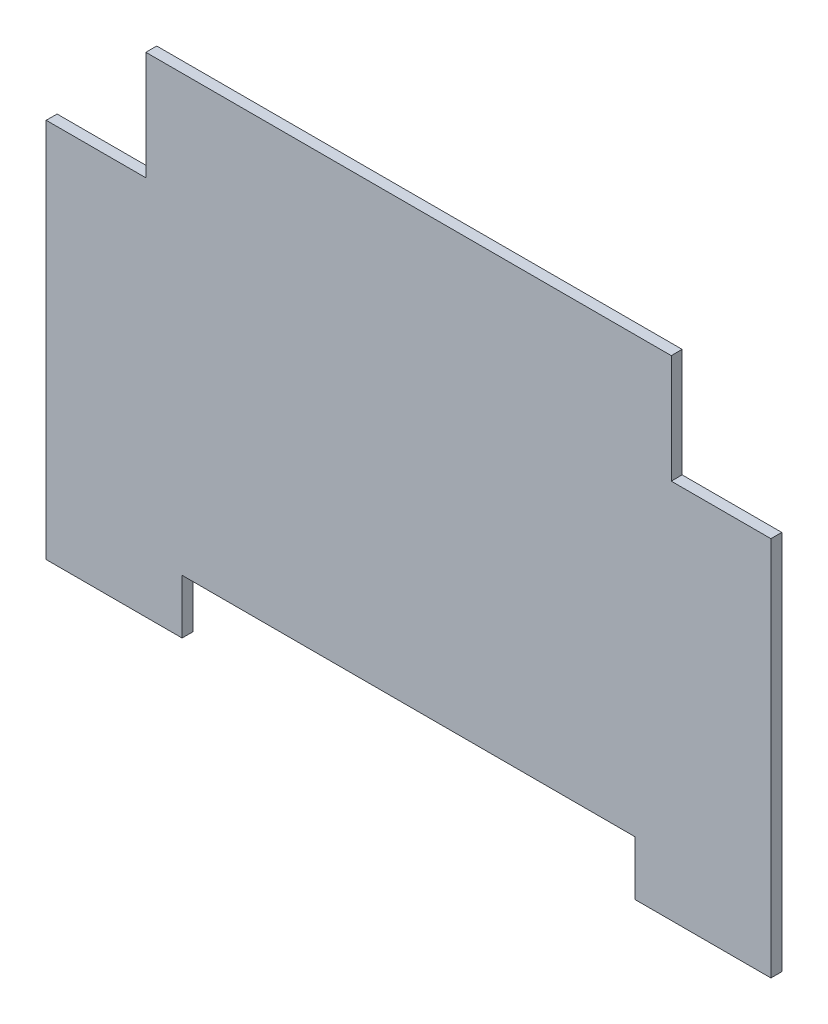
SolidWorks part; units mm, degrees
material "Pine"
ref_plane "Front Plane" through (0, 0, 0) normal (0, 0, 1) x (1, 0, 0)
ref_plane "Top Plane" through (0, 0, 0) normal (0, 1, 0) x (1, 0, 0)
ref_plane "Right Plane" through (0, 0, 0) normal (1, 0, 0) x (0, 0, -1)
sketch "Sketch1" plane through (0, 0, 0) normal (0, 0, 1) x (1, 0, 0)
  line L1 (-110.8686, 260.6668) -> (289.1314, 260.6668)
  line L2 (-110.8686, 260.6668) -> (-110.8686, -9.3332)
  line L3 (-110.8686, -9.3332) -> (289.1314, -9.3332)
  line L4 (289.1314, 260.6668) -> (289.1314, -9.3332)
  dimension "D1" = 400
  dimension "D2" = 270
extrude "Boss-Extrude1" add sketch "Sketch1" along normal blind 6
sketch "Sketch2" plane through (0, 0, 0) normal (0, 0, -1) x (-1, 0, 0)
  line L1 (-289.1314, 200.6668) -> (-234.1314, 200.6668)
  line L2 (-289.1314, 200.6668) -> (-289.1314, 260.6668)
  line L3 (-289.1314, 260.6668) -> (-234.1314, 260.6668)
  line L4 (-234.1314, 200.6668) -> (-234.1314, 260.6668)
  line L5 (110.8686, 200.6668) -> (55.8686, 200.6668)
  line L6 (110.8686, 200.6668) -> (110.8686, 260.6668)
  line L7 (110.8686, 260.6668) -> (55.8686, 260.6668)
  line L8 (55.8686, 200.6668) -> (55.8686, 260.6668)
  line L9 (110.8686, 260.6668) -> (110.8686, -9.3332) construction
  line L10 (-289.1314, 260.6668) -> (110.8686, 260.6668) construction
  line L11 (-289.1314, -9.3332) -> (-289.1314, 260.6668) construction
  dimension "D1" = 55
  dimension "D2" = 55
  dimension "D3" = 60
  dimension "D4" = 60
  dimension "D5" = 0
  dimension "D6" = 0
  dimension "D7" = 0
  dimension "D8" = 0
extrude "Cut-Extrude1" cut sketch "Sketch2" against normal blind 40
sketch "Sketch3" plane through (0, 0, 0) normal (0, 0, -1) x (-1, 0, 0)
  line L0 (110.8686, -9.3332) -> (-289.1314, -9.3332) construction
  line L1 (35.8686, 20.6668) -> (-214.1314, 20.6668)
  line L2 (35.8686, 20.6668) -> (35.8686, -9.3332)
  line L3 (35.8686, -9.3332) -> (-214.1314, -9.3332)
  line L4 (-214.1314, 20.6668) -> (-214.1314, -9.3332)
  line L5 (-289.1314, -9.3332) -> (-289.1314, 200.6668) construction
  dimension "D1" = 0
  dimension "D2" = 250
  dimension "D3" = 30
  dimension "D4" = 75
extrude "Cut-Extrude2" cut sketch "Sketch3" against normal blind 10
